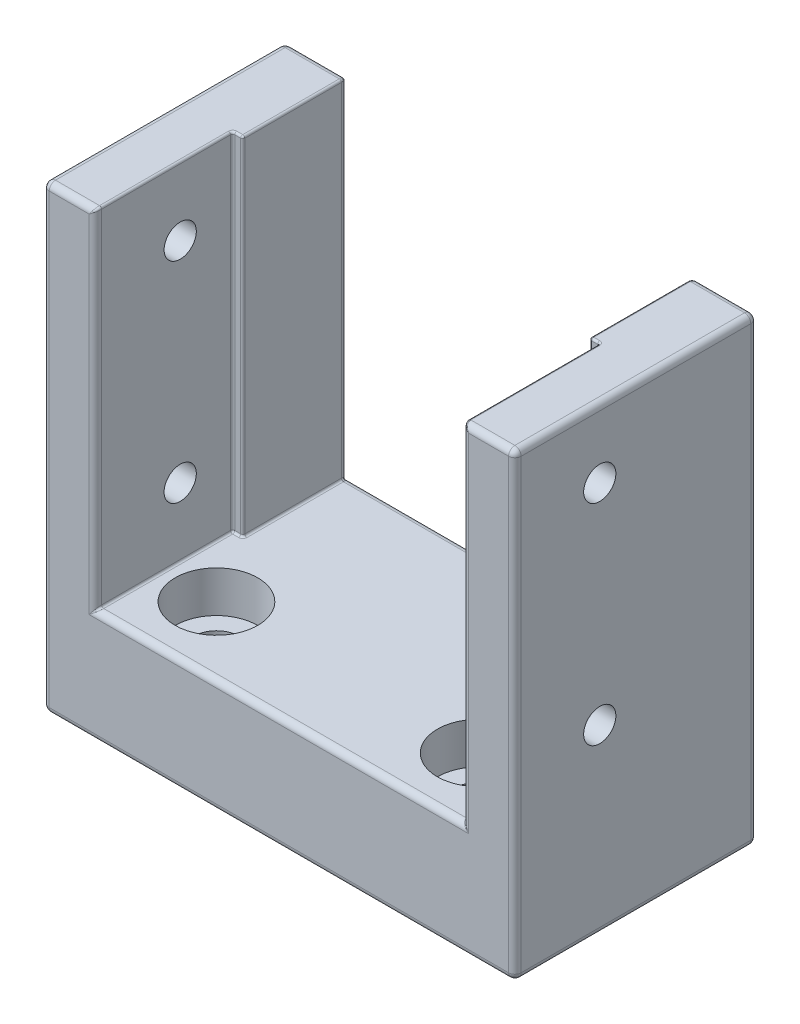
SolidWorks part; units mm, degrees
material "ABS"
ref_plane "Front Plane" through (0, 0, 0) normal (0, 0, 1) x (1, 0, 0)
ref_plane "Top Plane" through (0, 0, 0) normal (0, 1, 0) x (1, 0, 0)
ref_plane "Right Plane" through (0, 0, 0) normal (1, 0, 0) x (0, 0, -1)
sketch "Sketch1" plane through (0, 0, 0) normal (0, 1, 0) x (1, 0, 0)
  line L1 (-22.225, 14.6625) -> (22.225, 14.6625)
  line L2 (-22.225, 14.6625) -> (-22.225, -14.6625)
  line L3 (-22.225, -14.6625) -> (22.225, -14.6625)
  line L4 (22.225, 14.6625) -> (22.225, -14.6625)
  point P4 (0, -14.6625)
  point P6 (-22.225, 0)
  dimension "D1" = 29.325
  dimension "D2" = 44.45
extrude "Boss-Extrude1" add sketch "Sketch1" against normal blind 13.685
sketch "Sketch2" plane through (22.225, 0, 0) normal (1, 0, 0) x (0, 0, -1)
  line L0 (14.6625, -13.685) -> (14.6625, 0) construction
  line L1 (-14.6625, -13.685) -> (14.6625, -13.685)
  line L2 (-14.6625, -13.685) -> (-14.6625, 42)
  line L3 (-14.6625, 42) -> (14.6625, 42)
  line L4 (14.6625, -13.685) -> (14.6625, 42)
  point P5 (26.1247, 39.4701)
  point P6 (26.1247, 14.0701)
  dimension "D1" = 55.685
extrude "Boss-Extrude2" add sketch "Sketch2" along normal blind 6.35
hole_wizard "M3.5 Clearance Hole1" positions "Sketch5" profile "Sketch6" hole size "M3.5" standard "ANSI Metric" end condition through all
sketch "Sketch5" plane through (28.575, 0, 0) normal (1, 0, 0) x (0, 0, -1)
  line L1 (14.6625, 42) -> (-14.6625, 42) construction
  line L2 (-14.6625, 42) -> (-14.6625, -13.685) construction
  point P0 (-4.3875, 33.7)
  point P2 (-4.3875, 8.3)
  dimension "D1" = 10.275
  dimension "D2" = 8.3
  dimension "D3" = 25.4
sketch "Sketch6" plane through (28.575, 33.7, 4.3875) normal (0, 1, 0) x (0, 0, -1)
  line L0 (0, 0) -> (0, 50.8)
  line L1 (0, 50.8) -> (1.95, 50.8)
  line L2 (1.95, 50.8) -> (1.95, 0)
  line L5 (1.95, 0) -> (0, 0)
  line L11 (0, -6.35) -> (0, 107.95) construction
  dimension "Thru Hole Dia." = 3.9
  dimension "Thru Hole Depth" = 50.8
mirror "Mirror1" about plane through (0, 0, 0) normal (1, 0, 0) of "Boss-Extrude2", "M3.5 Clearance Hole1"
sketch "Sketch8" plane through (22.225, 0, 0) normal (-1, 0, 0) x (0, 0, 1)
  line L0 (-14.6625, 42) -> (14.6625, 42) construction
  line L1 (-14.6625, 0) -> (-1.9625, 0)
  line L2 (-14.6625, 0) -> (-14.6625, 42)
  line L3 (-14.6625, 42) -> (-1.9625, 42)
  line L4 (-1.9625, 0) -> (-1.9625, 42)
  dimension "D1" = 12.7
extrude "Boss-Extrude6" add sketch "Sketch8" along normal blind 1.225
mirror "Mirror2" about plane through (0, 0, 0) normal (1, 0, 0) of "Boss-Extrude6"
hole_wizard "CBORE for M5 SHCS1" positions "Sketch9" profile "Sketch10" counterbore size "M5" standard "ANSI Metric" end condition through all
sketch "Sketch9" plane through (0, 0, 0) normal (0, 1, 0) x (1, 0, 0)
  line L0 (-22.225, 1.9625) -> (-22.225, -14.6625) construction
  line L1 (0, -16.1288) -> (0, 16.1288) construction
  point P0 (15.875, -6.35)
  point P2 (-15.875, -6.35)
  point P8 (-22.225, -6.35)
  dimension "D1" = 15.875
  dimension "D2" = 15.875
sketch "Sketch10" plane through (15.875, 0, 6.35) normal (1, 0, 0) x (0, 0, 1)
  line L0 (0, 0) -> (0, 13.685)
  line L1 (0, 13.685) -> (2.75, 13.685)
  line L3 (2.75, 13.685) -> (2.75, 5)
  line L4 (2.75, 5) -> (5, 5)
  line L5 (5, 5) -> (5, 0)
  line L7 (5, 0) -> (0, 0)
  line L11 (0, -6.35) -> (0, 107.95) construction
  dimension "Thru Hole Dia." = 5.5
  dimension "Thru Hole Depth" = 13.685
  dimension "C'Bore Dia." = 10
  dimension "C'Bore Depth" = 5
fillet "Fillet1" radius 0.762 22 edges at (-21, 21, -14.6625) (-24.7875, 42, -14.6625) (-28.575, 14.1575, -14.6625) (28.575, 14.1575, -14.6625) (24.7875, 42, -14.6625) (21, 21, -14.6625) (0, 0, -14.6625) (22.225, 21, 14.6625) (25.4, 42, 14.6625) (28.575, 14.1575, 14.6625) (-28.575, 14.1575, 14.6625) (-25.4, 42, 14.6625) (-22.225, 21, 14.6625) (0, 0, 14.6625) (28.575, -13.685, 0) (0, -13.685, -14.6625) (-28.575, -13.685, 0) (0, -13.685, 14.6625) (-15.875, -13.685, 9.1) (15.875, -13.685, 9.1) (28.575, 42, 0) (-28.575, 42, 0)
fillet "Fillet2" radius 0.254 24 edges at (-21.2232, -0.2232, -14.4393) (21.2232, -0.2232, -14.4393) (22.4482, 41.7768, 14.4393) (-21, 0, -7.9315) (21, 0, -7.9315) (22.225, 42, 5.969) (-22.4482, -0.2232, 14.4393) (-21.2232, 41.7768, -14.4393) (-22.4482, 41.7768, 14.4393) (22.4482, -0.2232, 14.4393) (21.2232, 41.7768, -14.4393) (-22.225, 0, 5.969) (-21.6125, 0, -1.9625) (-21, 42, -7.9315) (-21, 21, -1.9625) (-22.225, 21, -1.9625) (-21.6125, 42, -1.9625) (-22.225, 42, 5.969) (21.6125, 0, -1.9625) (22.225, 0, 5.969) (21.6125, 42, -1.9625) (21, 21, -1.9625) (22.225, 21, -1.9625) (21, 42, -7.9315)
